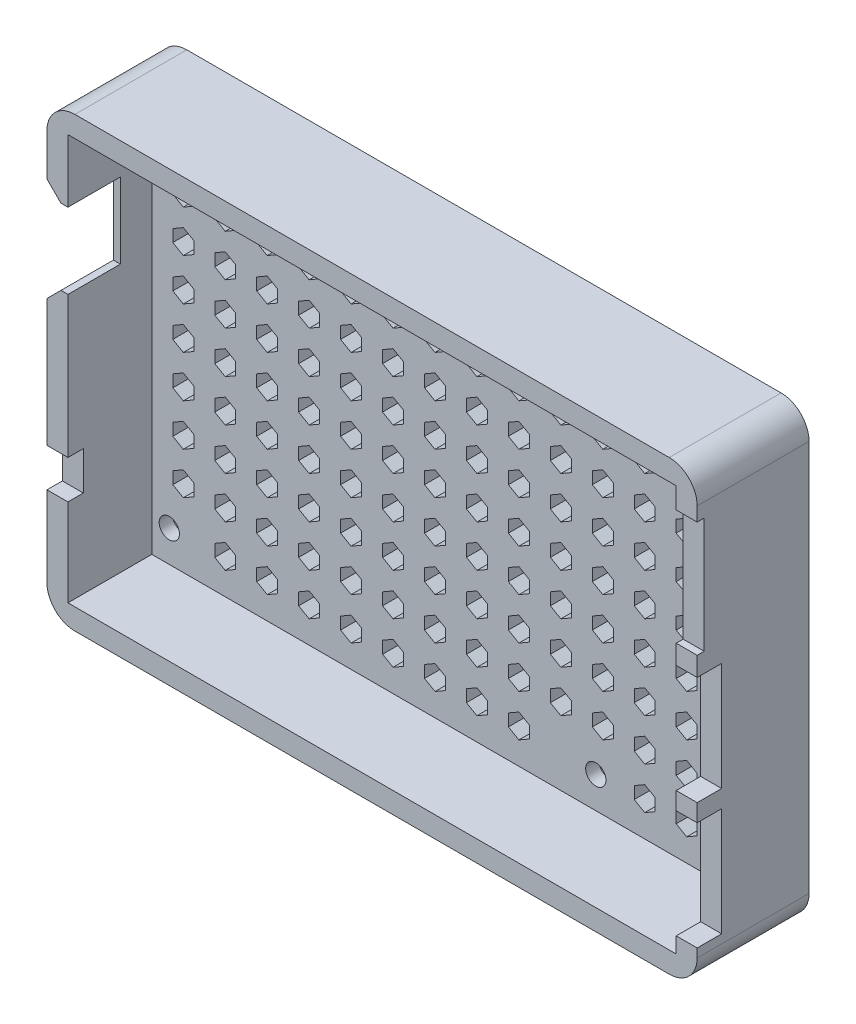
SolidWorks part; units mm, degrees
ref_plane "Přední rovina" through (0, 0, 0) normal (0, 0, 1) x (1, 0, 0)
ref_plane "Horní rovina" through (0, 0, 0) normal (0, 1, 0) x (1, 0, 0)
ref_plane "Pravá rovina" through (0, 0, 0) normal (1, 0, 0) x (0, 0, -1)
sketch "Base sketch" plane through (0, 0, 0) normal (0, 0, 1) x (1, 0, 0)
  line L1 (-46.5, 32) -> (46.5, 32)
  line L2 (-46.5, 32) -> (-46.5, -32)
  line L3 (-46.5, -32) -> (46.5, -32)
  line L4 (46.5, 32) -> (46.5, -32)
  line L5 (-46.5, 32) -> (46.5, -32) construction
  line L6 (-46.5, -32) -> (46.5, 32) construction
  point P0 (0, 0)
  dimension "D1" = 93
  dimension "D2" = 64
extrude "Base" add sketch "Base sketch" along normal blind 16
sketch "Inside cut sketch" plane through (0, 0, 16) normal (0, 0, 1) x (1, 0, 0)
  line L1 (-43.5, 29) -> (43.5, 29)
  line L2 (-43.5, 29) -> (-43.5, -29)
  line L3 (-43.5, -29) -> (43.5, -29)
  line L4 (43.5, 29) -> (43.5, -29)
  line L5 (-43.5, 29) -> (43.5, -29) construction
  line L6 (-43.5, -29) -> (43.5, 29) construction
  point P0 (0, 0)
  dimension "D1" = 58
  dimension "D2" = 87
extrude "Inside cut" cut sketch "Inside cut sketch" against normal blind 12
sketch "Front connectors sketch" plane through (46.5, 0, 0) normal (1, 0, 0) x (0, 0, -1)
  line L0 (-15, -32) -> (-15, 32)
  line L1 (-16, -32) -> (0, -32) construction
  line L2 (-16, 32) -> (0, 32) construction
  line L3 (-12.5, -32) -> (-12.5, 32)
  line L4 (-16, -32) -> (-16, 32) construction
  line L5 (-15, 26) -> (-16, 26)
  line L6 (-15, 26) -> (-15, 9.5)
  line L7 (-15, 9.5) -> (-16, 9.5)
  line L8 (-16, 26) -> (-16, 9.5)
  line L10 (-12.5, 6.75) -> (-16, 6.75)
  line L11 (-12.5, 6.75) -> (-12.5, -8.75)
  line L12 (-12.5, -8.75) -> (-16, -8.75)
  line L13 (-16, 6.75) -> (-16, -8.75)
  line L14 (-12.5, -11.25) -> (-16, -11.25)
  line L15 (-12.5, -11.25) -> (-12.5, -26.75)
  line L16 (-12.5, -26.75) -> (-16, -26.75)
  line L17 (-16, -11.25) -> (-16, -26.75)
  point P23 (-16, 17.75)
  point P25 (-16, -1)
  point P26 (-16, -19)
  dimension "D1" = 1
  dimension "D2" = 3.5
  dimension "D3" = 16.5
  dimension "D4" = 11.25
  dimension "D5" = 30
  dimension "D6" = 15.5
  dimension "D7" = 48
extrude "Front connectors" cut sketch "Front connectors sketch" against normal up to next contours L14 L17 L16 L15 | L12 L13 L10 L11 | L8 L7 L6 L5
sketch "Back connectors sketch" plane through (-46.5, 0, 0) normal (-1, 0, 0) x (0, 0, 1)
  line L0 (16, 32) -> (16, -32) construction
  line L1 (16, 20) -> (8.5, 20)
  line L2 (16, 20) -> (16, 9.2)
  line L3 (16, 9.2) -> (8.5, 9.2)
  line L4 (8.5, 20) -> (8.5, 9.2)
  line L6 (16, -11) -> (13.8, -11)
  line L7 (16, -11) -> (16, -16.5)
  line L8 (16, -16.5) -> (13.8, -16.5)
  line L9 (13.8, -11) -> (13.8, -16.5)
  dimension "D1" = 15.5
  dimension "D2" = 5.5
  dimension "D3" = 2.2
  dimension "D4" = 12
  dimension "D5" = 10.8
  dimension "D6" = 7.5
extrude "Back connectors" cut sketch "Back connectors sketch" against normal up to next
chamfer "Molex angle" distance 2 angle 45 3 edges at (-46.5, 9.2, 12.25) (-46.5, 20, 12.25) (-46.5, 14.6, 8.5)
sketch "Screw holes sketch" plane through (0, 0, 0) normal (0, 0, -1) x (-1, 0, 0)
  line L1 (-20, 24.5) -> (41, 24.5)
  line L2 (-20, 24.5) -> (-20, -24.5)
  line L3 (-20, -24.5) -> (41, -24.5)
  line L4 (41, 24.5) -> (41, -24.5)
  line L5 (-20, 24.5) -> (41, -24.5) construction
  line L6 (-20, -24.5) -> (41, 24.5) construction
  point P0 (10.5, 0)
  dimension "D1" = 5.5
  dimension "D2" = 7.5
  dimension "D3" = 49
  dimension "D4" = 61
hole_wizard "Screw holes" positions "Skica6" profile "Skica7" counterbore size "M2.5" standard "ISO" end condition through all
sketch "Skica6" plane through (0, 0, 0) normal (0, 0, -1) x (-1, 0, 0)
  point P0 (-20, -24.5)
  point P3 (-20, 24.5)
  point P6 (41, 24.5)
  point P9 (41, -24.5)
sketch "Skica7" plane through (20, -24.5, 0) normal (1, 0, 0) x (0, 1, 0)
  line L0 (0, 0) -> (0, 16)
  line L1 (0, 16) -> (1.45, 16)
  line L3 (1.45, 16) -> (1.45, 2.1)
  line L4 (1.45, 2.1) -> (3, 2.1)
  line L5 (3, 2.1) -> (3, 0)
  line L7 (3, 0) -> (0, 0)
  line L11 (0, -6.35) -> (0, 107.95) construction
  dimension "Průměr díry skrz" = 2.9
  dimension "Hloubka díry skrz" = 16
  dimension "Průměr válcového zahloubení" = 6
  dimension "Hloubka válcového zahloubení" = 2.1
fillet "Box rounding" radius 4 4 edges at (-46.5, -32, 8) (-46.5, 32, 8) (46.5, 32, 8) (46.5, -32, 8)
sketch "Ventilation holes sketch" plane through (0, 0, 0) normal (0, 0, -1) x (-1, 0, 0)
  line L0 (-42.5, 32) -> (42.5, 32) construction
  line L1 (-39, 22.2659) -> (-37.5, 23.1319)
  line L2 (-37.5, 23.1319) -> (-37.5, 24.864)
  line L3 (-37.5, 24.864) -> (-39, 25.73)
  line L4 (-39, 25.73) -> (-40.5, 24.864)
  line L5 (-40.5, 24.864) -> (-40.5, 23.1319)
  line L6 (-40.5, 23.1319) -> (-39, 22.2659)
  line L7 (-46.5, -28) -> (-46.5, 28) construction
  line L8 (-33, 22.2659) -> (-31.5, 23.1319)
  line L9 (-31.5, 23.1319) -> (-31.5, 24.864)
  line L10 (-31.5, 24.864) -> (-33, 25.73)
  line L11 (-33, 25.73) -> (-34.5, 24.864)
  line L12 (-34.5, 24.864) -> (-34.5, 23.1319)
  line L13 (-34.5, 23.1319) -> (-33, 22.2659)
  line L14 (-27, 22.2659) -> (-25.5, 23.1319)
  line L15 (-25.5, 23.1319) -> (-25.5, 24.864)
  line L16 (-25.5, 24.864) -> (-27, 25.73)
  line L17 (-27, 25.73) -> (-28.5, 24.864)
  line L18 (-28.5, 24.864) -> (-28.5, 23.1319)
  line L19 (-28.5, 23.1319) -> (-27, 22.2659)
  line L20 (-21, 22.2659) -> (-19.5, 23.1319)
  line L21 (-19.5, 23.1319) -> (-19.5, 24.864)
  line L22 (-19.5, 24.864) -> (-21, 25.73)
  line L23 (-21, 25.73) -> (-22.5, 24.864)
  line L24 (-22.5, 24.864) -> (-22.5, 23.1319)
  line L25 (-22.5, 23.1319) -> (-21, 22.2659)
  line L26 (-15, 22.2659) -> (-13.5, 23.1319)
  line L27 (-13.5, 23.1319) -> (-13.5, 24.864)
  line L28 (-13.5, 24.864) -> (-15, 25.73)
  line L29 (-15, 25.73) -> (-16.5, 24.864)
  line L30 (-16.5, 24.864) -> (-16.5, 23.1319)
  line L31 (-16.5, 23.1319) -> (-15, 22.2659)
  line L32 (-9, 22.2659) -> (-7.5, 23.1319)
  line L33 (-7.5, 23.1319) -> (-7.5, 24.864)
  line L34 (-7.5, 24.864) -> (-9, 25.73)
  line L35 (-9, 25.73) -> (-10.5, 24.864)
  line L36 (-10.5, 24.864) -> (-10.5, 23.1319)
  line L37 (-10.5, 23.1319) -> (-9, 22.2659)
  line L38 (-3, 22.2659) -> (-1.5, 23.1319)
  line L39 (-1.5, 23.1319) -> (-1.5, 24.864)
  line L40 (-1.5, 24.864) -> (-3, 25.73)
  line L41 (-3, 25.73) -> (-4.5, 24.864)
  line L42 (-4.5, 24.864) -> (-4.5, 23.1319)
  line L43 (-4.5, 23.1319) -> (-3, 22.2659)
  line L44 (3, 22.2659) -> (4.5, 23.1319)
  line L45 (4.5, 23.1319) -> (4.5, 24.864)
  line L46 (4.5, 24.864) -> (3, 25.73)
  line L47 (3, 25.73) -> (1.5, 24.864)
  line L48 (1.5, 24.864) -> (1.5, 23.1319)
  line L49 (1.5, 23.1319) -> (3, 22.2659)
  line L50 (9, 22.2659) -> (10.5, 23.1319)
  line L51 (10.5, 23.1319) -> (10.5, 24.864)
  line L52 (10.5, 24.864) -> (9, 25.73)
  line L53 (9, 25.73) -> (7.5, 24.864)
  line L54 (7.5, 24.864) -> (7.5, 23.1319)
  line L55 (7.5, 23.1319) -> (9, 22.2659)
  line L56 (15, 22.2659) -> (16.5, 23.1319)
  line L57 (16.5, 23.1319) -> (16.5, 24.864)
  line L58 (16.5, 24.864) -> (15, 25.73)
  line L59 (15, 25.73) -> (13.5, 24.864)
  line L60 (13.5, 24.864) -> (13.5, 23.1319)
  line L61 (13.5, 23.1319) -> (15, 22.2659)
  line L62 (21, 22.2659) -> (22.5, 23.1319)
  line L63 (22.5, 23.1319) -> (22.5, 24.864)
  line L64 (22.5, 24.864) -> (21, 25.73)
  line L65 (21, 25.73) -> (19.5, 24.864)
  line L66 (19.5, 24.864) -> (19.5, 23.1319)
  line L67 (19.5, 23.1319) -> (21, 22.2659)
  line L68 (27, 22.2659) -> (28.5, 23.1319)
  line L69 (28.5, 23.1319) -> (28.5, 24.864)
  line L70 (28.5, 24.864) -> (27, 25.73)
  line L71 (27, 25.73) -> (25.5, 24.864)
  line L72 (25.5, 24.864) -> (25.5, 23.1319)
  line L73 (25.5, 23.1319) -> (27, 22.2659)
  line L74 (33, 22.2659) -> (34.5, 23.1319)
  line L75 (34.5, 23.1319) -> (34.5, 24.864)
  line L76 (34.5, 24.864) -> (33, 25.73)
  line L77 (33, 25.73) -> (31.5, 24.864)
  line L78 (31.5, 24.864) -> (31.5, 23.1319)
  line L79 (31.5, 23.1319) -> (33, 22.2659)
  line L80 (39, 22.2659) -> (40.5, 23.1319)
  line L81 (40.5, 23.1319) -> (40.5, 24.864)
  line L82 (40.5, 24.864) -> (39, 25.73)
  line L83 (39, 25.73) -> (37.5, 24.864)
  line L84 (37.5, 24.864) -> (37.5, 23.1319)
  line L85 (37.5, 23.1319) -> (39, 22.2659)
  line L86 (-33, 16.2659) -> (-31.5, 17.1319)
  line L87 (-31.5, 17.1319) -> (-31.5, 18.864)
  line L88 (-31.5, 18.864) -> (-33, 19.73)
  line L89 (-33, 19.73) -> (-34.5, 18.864)
  line L90 (-34.5, 18.864) -> (-34.5, 17.1319)
  line L91 (-34.5, 17.1319) -> (-33, 16.2659)
  line L92 (-27, 16.2659) -> (-25.5, 17.1319)
  line L93 (-25.5, 17.1319) -> (-25.5, 18.864)
  line L94 (-25.5, 18.864) -> (-27, 19.73)
  line L95 (-27, 19.73) -> (-28.5, 18.864)
  line L96 (-28.5, 18.864) -> (-28.5, 17.1319)
  line L97 (-28.5, 17.1319) -> (-27, 16.2659)
  line L98 (-21, 16.2659) -> (-19.5, 17.1319)
  line L99 (-19.5, 17.1319) -> (-19.5, 18.864)
  line L100 (-19.5, 18.864) -> (-21, 19.73)
  line L101 (-21, 19.73) -> (-22.5, 18.864)
  line L102 (-22.5, 18.864) -> (-22.5, 17.1319)
  line L103 (-22.5, 17.1319) -> (-21, 16.2659)
  line L104 (-15, 16.2659) -> (-13.5, 17.1319)
  line L105 (-13.5, 17.1319) -> (-13.5, 18.864)
  line L106 (-13.5, 18.864) -> (-15, 19.73)
  line L107 (-15, 19.73) -> (-16.5, 18.864)
  line L108 (-16.5, 18.864) -> (-16.5, 17.1319)
  line L109 (-16.5, 17.1319) -> (-15, 16.2659)
  line L110 (-9, 16.2659) -> (-7.5, 17.1319)
  line L111 (-7.5, 17.1319) -> (-7.5, 18.864)
  line L112 (-7.5, 18.864) -> (-9, 19.73)
  line L113 (-9, 19.73) -> (-10.5, 18.864)
  line L114 (-10.5, 18.864) -> (-10.5, 17.1319)
  line L115 (-10.5, 17.1319) -> (-9, 16.2659)
  line L116 (-3, 16.2659) -> (-1.5, 17.1319)
  line L117 (-1.5, 17.1319) -> (-1.5, 18.864)
  line L118 (-1.5, 18.864) -> (-3, 19.73)
  line L119 (-3, 19.73) -> (-4.5, 18.864)
  line L120 (-4.5, 18.864) -> (-4.5, 17.1319)
  line L121 (-4.5, 17.1319) -> (-3, 16.2659)
  line L122 (3, 16.2659) -> (4.5, 17.1319)
  line L123 (4.5, 17.1319) -> (4.5, 18.864)
  line L124 (4.5, 18.864) -> (3, 19.73)
  line L125 (3, 19.73) -> (1.5, 18.864)
  line L126 (1.5, 18.864) -> (1.5, 17.1319)
  line L127 (1.5, 17.1319) -> (3, 16.2659)
  line L128 (9, 16.2659) -> (10.5, 17.1319)
  line L129 (10.5, 17.1319) -> (10.5, 18.864)
  line L130 (10.5, 18.864) -> (9, 19.73)
  line L131 (9, 19.73) -> (7.5, 18.864)
  line L132 (7.5, 18.864) -> (7.5, 17.1319)
  line L133 (7.5, 17.1319) -> (9, 16.2659)
  line L134 (15, 16.2659) -> (16.5, 17.1319)
  line L135 (16.5, 17.1319) -> (16.5, 18.864)
  line L136 (16.5, 18.864) -> (15, 19.73)
  line L137 (15, 19.73) -> (13.5, 18.864)
  line L138 (13.5, 18.864) -> (13.5, 17.1319)
  line L139 (13.5, 17.1319) -> (15, 16.2659)
  line L140 (21, 16.2659) -> (22.5, 17.1319)
  line L141 (22.5, 17.1319) -> (22.5, 18.864)
  line L142 (22.5, 18.864) -> (21, 19.73)
  line L143 (21, 19.73) -> (19.5, 18.864)
  line L144 (19.5, 18.864) -> (19.5, 17.1319)
  line L145 (19.5, 17.1319) -> (21, 16.2659)
  line L146 (27, 16.2659) -> (28.5, 17.1319)
  line L147 (28.5, 17.1319) -> (28.5, 18.864)
  line L148 (28.5, 18.864) -> (27, 19.73)
  line L149 (27, 19.73) -> (25.5, 18.864)
  line L150 (25.5, 18.864) -> (25.5, 17.1319)
  line L151 (25.5, 17.1319) -> (27, 16.2659)
  line L152 (33, 16.2659) -> (34.5, 17.1319)
  line L153 (34.5, 17.1319) -> (34.5, 18.864)
  line L154 (34.5, 18.864) -> (33, 19.73)
  line L155 (33, 19.73) -> (31.5, 18.864)
  line L156 (31.5, 18.864) -> (31.5, 17.1319)
  line L157 (31.5, 17.1319) -> (33, 16.2659)
  line L158 (39, 16.2659) -> (40.5, 17.1319)
  line L159 (40.5, 17.1319) -> (40.5, 18.864)
  line L160 (40.5, 18.864) -> (39, 19.73)
  line L161 (39, 19.73) -> (37.5, 18.864)
  line L162 (37.5, 18.864) -> (37.5, 17.1319)
  line L163 (37.5, 17.1319) -> (39, 16.2659)
  line L164 (-33, 10.2659) -> (-31.5, 11.1319)
  line L165 (-31.5, 11.1319) -> (-31.5, 12.864)
  line L166 (-31.5, 12.864) -> (-33, 13.73)
  line L167 (-33, 13.73) -> (-34.5, 12.864)
  line L168 (-34.5, 12.864) -> (-34.5, 11.1319)
  line L169 (-34.5, 11.1319) -> (-33, 10.2659)
  line L170 (-27, 10.2659) -> (-25.5, 11.1319)
  line L171 (-25.5, 11.1319) -> (-25.5, 12.864)
  line L172 (-25.5, 12.864) -> (-27, 13.73)
  line L173 (-27, 13.73) -> (-28.5, 12.864)
  line L174 (-28.5, 12.864) -> (-28.5, 11.1319)
  line L175 (-28.5, 11.1319) -> (-27, 10.2659)
  line L176 (-21, 10.2659) -> (-19.5, 11.1319)
  line L177 (-19.5, 11.1319) -> (-19.5, 12.864)
  line L178 (-19.5, 12.864) -> (-21, 13.73)
  line L179 (-21, 13.73) -> (-22.5, 12.864)
  line L180 (-22.5, 12.864) -> (-22.5, 11.1319)
  line L181 (-22.5, 11.1319) -> (-21, 10.2659)
  line L182 (-15, 10.2659) -> (-13.5, 11.1319)
  line L183 (-13.5, 11.1319) -> (-13.5, 12.864)
  line L184 (-13.5, 12.864) -> (-15, 13.73)
  line L185 (-15, 13.73) -> (-16.5, 12.864)
  line L186 (-16.5, 12.864) -> (-16.5, 11.1319)
  line L187 (-16.5, 11.1319) -> (-15, 10.2659)
  line L188 (-9, 10.2659) -> (-7.5, 11.1319)
  line L189 (-7.5, 11.1319) -> (-7.5, 12.864)
  line L190 (-7.5, 12.864) -> (-9, 13.73)
  line L191 (-9, 13.73) -> (-10.5, 12.864)
  line L192 (-10.5, 12.864) -> (-10.5, 11.1319)
  line L193 (-10.5, 11.1319) -> (-9, 10.2659)
  line L194 (-3, 10.2659) -> (-1.5, 11.1319)
  line L195 (-1.5, 11.1319) -> (-1.5, 12.864)
  line L196 (-1.5, 12.864) -> (-3, 13.73)
  line L197 (-3, 13.73) -> (-4.5, 12.864)
  line L198 (-4.5, 12.864) -> (-4.5, 11.1319)
  line L199 (-4.5, 11.1319) -> (-3, 10.2659)
  line L200 (3, 10.2659) -> (4.5, 11.1319)
  line L201 (4.5, 11.1319) -> (4.5, 12.864)
  line L202 (4.5, 12.864) -> (3, 13.73)
  line L203 (3, 13.73) -> (1.5, 12.864)
  line L204 (1.5, 12.864) -> (1.5, 11.1319)
  line L205 (1.5, 11.1319) -> (3, 10.2659)
  line L206 (9, 10.2659) -> (10.5, 11.1319)
  line L207 (10.5, 11.1319) -> (10.5, 12.864)
  line L208 (10.5, 12.864) -> (9, 13.73)
  line L209 (9, 13.73) -> (7.5, 12.864)
  line L210 (7.5, 12.864) -> (7.5, 11.1319)
  line L211 (7.5, 11.1319) -> (9, 10.2659)
  line L212 (15, 10.2659) -> (16.5, 11.1319)
  line L213 (16.5, 11.1319) -> (16.5, 12.864)
  line L214 (16.5, 12.864) -> (15, 13.73)
  line L215 (15, 13.73) -> (13.5, 12.864)
  line L216 (13.5, 12.864) -> (13.5, 11.1319)
  line L217 (13.5, 11.1319) -> (15, 10.2659)
  line L218 (21, 10.2659) -> (22.5, 11.1319)
  line L219 (22.5, 11.1319) -> (22.5, 12.864)
  line L220 (22.5, 12.864) -> (21, 13.73)
  line L221 (21, 13.73) -> (19.5, 12.864)
  line L222 (19.5, 12.864) -> (19.5, 11.1319)
  line L223 (19.5, 11.1319) -> (21, 10.2659)
  line L224 (27, 10.2659) -> (28.5, 11.1319)
  line L225 (28.5, 11.1319) -> (28.5, 12.864)
  line L226 (28.5, 12.864) -> (27, 13.73)
  line L227 (27, 13.73) -> (25.5, 12.864)
  line L228 (25.5, 12.864) -> (25.5, 11.1319)
  line L229 (25.5, 11.1319) -> (27, 10.2659)
  line L230 (33, 10.2659) -> (34.5, 11.1319)
  line L231 (34.5, 11.1319) -> (34.5, 12.864)
  line L232 (34.5, 12.864) -> (33, 13.73)
  line L233 (33, 13.73) -> (31.5, 12.864)
  line L234 (31.5, 12.864) -> (31.5, 11.1319)
  line L235 (31.5, 11.1319) -> (33, 10.2659)
  line L236 (39, 10.2659) -> (40.5, 11.1319)
  line L237 (40.5, 11.1319) -> (40.5, 12.864)
  line L238 (40.5, 12.864) -> (39, 13.73)
  line L239 (39, 13.73) -> (37.5, 12.864)
  line L240 (37.5, 12.864) -> (37.5, 11.1319)
  line L241 (37.5, 11.1319) -> (39, 10.2659)
  line L242 (-33, 4.2659) -> (-31.5, 5.1319)
  line L243 (-31.5, 5.1319) -> (-31.5, 6.864)
  line L244 (-31.5, 6.864) -> (-33, 7.73)
  line L245 (-33, 7.73) -> (-34.5, 6.864)
  line L246 (-34.5, 6.864) -> (-34.5, 5.1319)
  line L247 (-34.5, 5.1319) -> (-33, 4.2659)
  line L248 (-27, 4.2659) -> (-25.5, 5.1319)
  line L249 (-25.5, 5.1319) -> (-25.5, 6.864)
  line L250 (-25.5, 6.864) -> (-27, 7.73)
  line L251 (-27, 7.73) -> (-28.5, 6.864)
  line L252 (-28.5, 6.864) -> (-28.5, 5.1319)
  line L253 (-28.5, 5.1319) -> (-27, 4.2659)
  line L254 (-21, 4.2659) -> (-19.5, 5.1319)
  line L255 (-19.5, 5.1319) -> (-19.5, 6.864)
  line L256 (-19.5, 6.864) -> (-21, 7.73)
  line L257 (-21, 7.73) -> (-22.5, 6.864)
  line L258 (-22.5, 6.864) -> (-22.5, 5.1319)
  line L259 (-22.5, 5.1319) -> (-21, 4.2659)
  line L260 (-15, 4.2659) -> (-13.5, 5.1319)
  line L261 (-13.5, 5.1319) -> (-13.5, 6.864)
  line L262 (-13.5, 6.864) -> (-15, 7.73)
  line L263 (-15, 7.73) -> (-16.5, 6.864)
  line L264 (-16.5, 6.864) -> (-16.5, 5.1319)
  line L265 (-16.5, 5.1319) -> (-15, 4.2659)
  line L266 (-9, 4.2659) -> (-7.5, 5.1319)
  line L267 (-7.5, 5.1319) -> (-7.5, 6.864)
  line L268 (-7.5, 6.864) -> (-9, 7.73)
  line L269 (-9, 7.73) -> (-10.5, 6.864)
  line L270 (-10.5, 6.864) -> (-10.5, 5.1319)
  line L271 (-10.5, 5.1319) -> (-9, 4.2659)
  line L272 (-3, 4.2659) -> (-1.5, 5.1319)
  line L273 (-1.5, 5.1319) -> (-1.5, 6.864)
  line L274 (-1.5, 6.864) -> (-3, 7.73)
  line L275 (-3, 7.73) -> (-4.5, 6.864)
  line L276 (-4.5, 6.864) -> (-4.5, 5.1319)
  line L277 (-4.5, 5.1319) -> (-3, 4.2659)
  line L278 (3, 4.2659) -> (4.5, 5.1319)
  line L279 (4.5, 5.1319) -> (4.5, 6.864)
  line L280 (4.5, 6.864) -> (3, 7.73)
  line L281 (3, 7.73) -> (1.5, 6.864)
  line L282 (1.5, 6.864) -> (1.5, 5.1319)
  line L283 (1.5, 5.1319) -> (3, 4.2659)
  line L284 (9, 4.2659) -> (10.5, 5.1319)
  line L285 (10.5, 5.1319) -> (10.5, 6.864)
  line L286 (10.5, 6.864) -> (9, 7.73)
  line L287 (9, 7.73) -> (7.5, 6.864)
  line L288 (7.5, 6.864) -> (7.5, 5.1319)
  line L289 (7.5, 5.1319) -> (9, 4.2659)
  line L290 (15, 4.2659) -> (16.5, 5.1319)
  line L291 (16.5, 5.1319) -> (16.5, 6.864)
  line L292 (16.5, 6.864) -> (15, 7.73)
  line L293 (15, 7.73) -> (13.5, 6.864)
  line L294 (13.5, 6.864) -> (13.5, 5.1319)
  line L295 (13.5, 5.1319) -> (15, 4.2659)
  line L296 (21, 4.2659) -> (22.5, 5.1319)
  line L297 (22.5, 5.1319) -> (22.5, 6.864)
  line L298 (22.5, 6.864) -> (21, 7.73)
  line L299 (21, 7.73) -> (19.5, 6.864)
  line L300 (19.5, 6.864) -> (19.5, 5.1319)
  line L301 (19.5, 5.1319) -> (21, 4.2659)
  line L302 (27, 4.2659) -> (28.5, 5.1319)
  line L303 (28.5, 5.1319) -> (28.5, 6.864)
  line L304 (28.5, 6.864) -> (27, 7.73)
  line L305 (27, 7.73) -> (25.5, 6.864)
  line L306 (25.5, 6.864) -> (25.5, 5.1319)
  line L307 (25.5, 5.1319) -> (27, 4.2659)
  line L308 (33, 4.2659) -> (34.5, 5.1319)
  line L309 (34.5, 5.1319) -> (34.5, 6.864)
  line L310 (34.5, 6.864) -> (33, 7.73)
  line L311 (33, 7.73) -> (31.5, 6.864)
  line L312 (31.5, 6.864) -> (31.5, 5.1319)
  line L313 (31.5, 5.1319) -> (33, 4.2659)
  line L314 (39, 4.2659) -> (40.5, 5.1319)
  line L315 (40.5, 5.1319) -> (40.5, 6.864)
  line L316 (40.5, 6.864) -> (39, 7.73)
  line L317 (39, 7.73) -> (37.5, 6.864)
  line L318 (37.5, 6.864) -> (37.5, 5.1319)
  line L319 (37.5, 5.1319) -> (39, 4.2659)
  line L320 (-33, -1.7341) -> (-31.5, -0.8681)
  line L321 (-31.5, -0.8681) -> (-31.5, 0.864)
  line L322 (-31.5, 0.864) -> (-33, 1.73)
  line L323 (-33, 1.73) -> (-34.5, 0.864)
  line L324 (-34.5, 0.864) -> (-34.5, -0.8681)
  line L325 (-34.5, -0.8681) -> (-33, -1.7341)
  line L326 (-27, -1.7341) -> (-25.5, -0.8681)
  line L327 (-25.5, -0.8681) -> (-25.5, 0.864)
  line L328 (-25.5, 0.864) -> (-27, 1.73)
  line L329 (-27, 1.73) -> (-28.5, 0.864)
  line L330 (-28.5, 0.864) -> (-28.5, -0.8681)
  line L331 (-28.5, -0.8681) -> (-27, -1.7341)
  line L332 (-21, -1.7341) -> (-19.5, -0.8681)
  line L333 (-19.5, -0.8681) -> (-19.5, 0.864)
  line L334 (-19.5, 0.864) -> (-21, 1.73)
  line L335 (-21, 1.73) -> (-22.5, 0.864)
  line L336 (-22.5, 0.864) -> (-22.5, -0.8681)
  line L337 (-22.5, -0.8681) -> (-21, -1.7341)
  line L338 (-15, -1.7341) -> (-13.5, -0.8681)
  line L339 (-13.5, -0.8681) -> (-13.5, 0.864)
  line L340 (-13.5, 0.864) -> (-15, 1.73)
  line L341 (-15, 1.73) -> (-16.5, 0.864)
  line L342 (-16.5, 0.864) -> (-16.5, -0.8681)
  line L343 (-16.5, -0.8681) -> (-15, -1.7341)
  line L344 (-9, -1.7341) -> (-7.5, -0.8681)
  line L345 (-7.5, -0.8681) -> (-7.5, 0.864)
  line L346 (-7.5, 0.864) -> (-9, 1.73)
  line L347 (-9, 1.73) -> (-10.5, 0.864)
  line L348 (-10.5, 0.864) -> (-10.5, -0.8681)
  line L349 (-10.5, -0.8681) -> (-9, -1.7341)
  line L350 (-3, -1.7341) -> (-1.5, -0.8681)
  line L351 (-1.5, -0.8681) -> (-1.5, 0.864)
  line L352 (-1.5, 0.864) -> (-3, 1.73)
  line L353 (-3, 1.73) -> (-4.5, 0.864)
  line L354 (-4.5, 0.864) -> (-4.5, -0.8681)
  line L355 (-4.5, -0.8681) -> (-3, -1.7341)
  line L356 (3, -1.7341) -> (4.5, -0.8681)
  line L357 (4.5, -0.8681) -> (4.5, 0.864)
  line L358 (4.5, 0.864) -> (3, 1.73)
  line L359 (3, 1.73) -> (1.5, 0.864)
  line L360 (1.5, 0.864) -> (1.5, -0.8681)
  line L361 (1.5, -0.8681) -> (3, -1.7341)
  line L362 (9, -1.7341) -> (10.5, -0.8681)
  line L363 (10.5, -0.8681) -> (10.5, 0.864)
  line L364 (10.5, 0.864) -> (9, 1.73)
  line L365 (9, 1.73) -> (7.5, 0.864)
  line L366 (7.5, 0.864) -> (7.5, -0.8681)
  line L367 (7.5, -0.8681) -> (9, -1.7341)
  line L368 (15, -1.7341) -> (16.5, -0.8681)
  line L369 (16.5, -0.8681) -> (16.5, 0.864)
  line L370 (16.5, 0.864) -> (15, 1.73)
  line L371 (15, 1.73) -> (13.5, 0.864)
  line L372 (13.5, 0.864) -> (13.5, -0.8681)
  line L373 (13.5, -0.8681) -> (15, -1.7341)
  line L374 (21, -1.7341) -> (22.5, -0.8681)
  line L375 (22.5, -0.8681) -> (22.5, 0.864)
  line L376 (22.5, 0.864) -> (21, 1.73)
  line L377 (21, 1.73) -> (19.5, 0.864)
  line L378 (19.5, 0.864) -> (19.5, -0.8681)
  line L379 (19.5, -0.8681) -> (21, -1.7341)
  line L380 (27, -1.7341) -> (28.5, -0.8681)
  line L381 (28.5, -0.8681) -> (28.5, 0.864)
  line L382 (28.5, 0.864) -> (27, 1.73)
  line L383 (27, 1.73) -> (25.5, 0.864)
  line L384 (25.5, 0.864) -> (25.5, -0.8681)
  line L385 (25.5, -0.8681) -> (27, -1.7341)
  line L386 (33, -1.7341) -> (34.5, -0.8681)
  line L387 (34.5, -0.8681) -> (34.5, 0.864)
  line L388 (34.5, 0.864) -> (33, 1.73)
  line L389 (33, 1.73) -> (31.5, 0.864)
  line L390 (31.5, 0.864) -> (31.5, -0.8681)
  line L391 (31.5, -0.8681) -> (33, -1.7341)
  line L392 (39, -1.7341) -> (40.5, -0.8681)
  line L393 (40.5, -0.8681) -> (40.5, 0.864)
  line L394 (40.5, 0.864) -> (39, 1.73)
  line L395 (39, 1.73) -> (37.5, 0.864)
  line L396 (37.5, 0.864) -> (37.5, -0.8681)
  line L397 (37.5, -0.8681) -> (39, -1.7341)
  line L398 (-33, -7.7341) -> (-31.5, -6.8681)
  line L399 (-31.5, -6.8681) -> (-31.5, -5.136)
  line L400 (-31.5, -5.136) -> (-33, -4.27)
  line L401 (-33, -4.27) -> (-34.5, -5.136)
  line L402 (-34.5, -5.136) -> (-34.5, -6.8681)
  line L403 (-34.5, -6.8681) -> (-33, -7.7341)
  line L404 (-27, -7.7341) -> (-25.5, -6.8681)
  line L405 (-25.5, -6.8681) -> (-25.5, -5.136)
  line L406 (-25.5, -5.136) -> (-27, -4.27)
  line L407 (-27, -4.27) -> (-28.5, -5.136)
  line L408 (-28.5, -5.136) -> (-28.5, -6.8681)
  line L409 (-28.5, -6.8681) -> (-27, -7.7341)
  line L410 (-21, -7.7341) -> (-19.5, -6.8681)
  line L411 (-19.5, -6.8681) -> (-19.5, -5.136)
  line L412 (-19.5, -5.136) -> (-21, -4.27)
  line L413 (-21, -4.27) -> (-22.5, -5.136)
  line L414 (-22.5, -5.136) -> (-22.5, -6.8681)
  line L415 (-22.5, -6.8681) -> (-21, -7.7341)
  line L416 (-15, -7.7341) -> (-13.5, -6.8681)
  line L417 (-13.5, -6.8681) -> (-13.5, -5.136)
  line L418 (-13.5, -5.136) -> (-15, -4.27)
  line L419 (-15, -4.27) -> (-16.5, -5.136)
  line L420 (-16.5, -5.136) -> (-16.5, -6.8681)
  line L421 (-16.5, -6.8681) -> (-15, -7.7341)
  line L422 (-9, -7.7341) -> (-7.5, -6.8681)
  line L423 (-7.5, -6.8681) -> (-7.5, -5.136)
  line L424 (-7.5, -5.136) -> (-9, -4.27)
  line L425 (-9, -4.27) -> (-10.5, -5.136)
  line L426 (-10.5, -5.136) -> (-10.5, -6.8681)
  line L427 (-10.5, -6.8681) -> (-9, -7.7341)
  line L428 (-3, -7.7341) -> (-1.5, -6.8681)
  line L429 (-1.5, -6.8681) -> (-1.5, -5.136)
  line L430 (-1.5, -5.136) -> (-3, -4.27)
  line L431 (-3, -4.27) -> (-4.5, -5.136)
  line L432 (-4.5, -5.136) -> (-4.5, -6.8681)
  line L433 (-4.5, -6.8681) -> (-3, -7.7341)
  line L434 (3, -7.7341) -> (4.5, -6.8681)
  line L435 (4.5, -6.8681) -> (4.5, -5.136)
  line L436 (4.5, -5.136) -> (3, -4.27)
  line L437 (3, -4.27) -> (1.5, -5.136)
  line L438 (1.5, -5.136) -> (1.5, -6.8681)
  line L439 (1.5, -6.8681) -> (3, -7.7341)
  line L440 (9, -7.7341) -> (10.5, -6.8681)
  line L441 (10.5, -6.8681) -> (10.5, -5.136)
  line L442 (10.5, -5.136) -> (9, -4.27)
  line L443 (9, -4.27) -> (7.5, -5.136)
  line L444 (7.5, -5.136) -> (7.5, -6.8681)
  line L445 (7.5, -6.8681) -> (9, -7.7341)
  line L446 (15, -7.7341) -> (16.5, -6.8681)
  line L447 (16.5, -6.8681) -> (16.5, -5.136)
  line L448 (16.5, -5.136) -> (15, -4.27)
  line L449 (15, -4.27) -> (13.5, -5.136)
  line L450 (13.5, -5.136) -> (13.5, -6.8681)
  line L451 (13.5, -6.8681) -> (15, -7.7341)
  line L452 (21, -7.7341) -> (22.5, -6.8681)
  line L453 (22.5, -6.8681) -> (22.5, -5.136)
  line L454 (22.5, -5.136) -> (21, -4.27)
  line L455 (21, -4.27) -> (19.5, -5.136)
  line L456 (19.5, -5.136) -> (19.5, -6.8681)
  line L457 (19.5, -6.8681) -> (21, -7.7341)
  line L458 (27, -7.7341) -> (28.5, -6.8681)
  line L459 (28.5, -6.8681) -> (28.5, -5.136)
  line L460 (28.5, -5.136) -> (27, -4.27)
  line L461 (27, -4.27) -> (25.5, -5.136)
  line L462 (25.5, -5.136) -> (25.5, -6.8681)
  line L463 (25.5, -6.8681) -> (27, -7.7341)
  line L464 (33, -7.7341) -> (34.5, -6.8681)
  line L465 (34.5, -6.8681) -> (34.5, -5.136)
  line L466 (34.5, -5.136) -> (33, -4.27)
  line L467 (33, -4.27) -> (31.5, -5.136)
  line L468 (31.5, -5.136) -> (31.5, -6.8681)
  line L469 (31.5, -6.8681) -> (33, -7.7341)
  line L470 (39, -7.7341) -> (40.5, -6.8681)
  line L471 (40.5, -6.8681) -> (40.5, -5.136)
  line L472 (40.5, -5.136) -> (39, -4.27)
  line L473 (39, -4.27) -> (37.5, -5.136)
  line L474 (37.5, -5.136) -> (37.5, -6.8681)
  line L475 (37.5, -6.8681) -> (39, -7.7341)
  line L476 (-33, -13.7341) -> (-31.5, -12.8681)
  line L477 (-31.5, -12.8681) -> (-31.5, -11.136)
  line L478 (-31.5, -11.136) -> (-33, -10.27)
  line L479 (-33, -10.27) -> (-34.5, -11.136)
  line L480 (-34.5, -11.136) -> (-34.5, -12.8681)
  line L481 (-34.5, -12.8681) -> (-33, -13.7341)
  line L482 (-27, -13.7341) -> (-25.5, -12.8681)
  line L483 (-25.5, -12.8681) -> (-25.5, -11.136)
  line L484 (-25.5, -11.136) -> (-27, -10.27)
  line L485 (-27, -10.27) -> (-28.5, -11.136)
  line L486 (-28.5, -11.136) -> (-28.5, -12.8681)
  line L487 (-28.5, -12.8681) -> (-27, -13.7341)
  line L488 (-21, -13.7341) -> (-19.5, -12.8681)
  line L489 (-19.5, -12.8681) -> (-19.5, -11.136)
  line L490 (-19.5, -11.136) -> (-21, -10.27)
  line L491 (-21, -10.27) -> (-22.5, -11.136)
  line L492 (-22.5, -11.136) -> (-22.5, -12.8681)
  line L493 (-22.5, -12.8681) -> (-21, -13.7341)
  line L494 (-15, -13.7341) -> (-13.5, -12.8681)
  line L495 (-13.5, -12.8681) -> (-13.5, -11.136)
  line L496 (-13.5, -11.136) -> (-15, -10.27)
  line L497 (-15, -10.27) -> (-16.5, -11.136)
  line L498 (-16.5, -11.136) -> (-16.5, -12.8681)
  line L499 (-16.5, -12.8681) -> (-15, -13.7341)
  line L500 (-9, -13.7341) -> (-7.5, -12.8681)
  line L501 (-7.5, -12.8681) -> (-7.5, -11.136)
  line L502 (-7.5, -11.136) -> (-9, -10.27)
  line L503 (-9, -10.27) -> (-10.5, -11.136)
  line L504 (-10.5, -11.136) -> (-10.5, -12.8681)
  line L505 (-10.5, -12.8681) -> (-9, -13.7341)
  line L506 (-3, -13.7341) -> (-1.5, -12.8681)
  line L507 (-1.5, -12.8681) -> (-1.5, -11.136)
  line L508 (-1.5, -11.136) -> (-3, -10.27)
  line L509 (-3, -10.27) -> (-4.5, -11.136)
  line L510 (-4.5, -11.136) -> (-4.5, -12.8681)
  line L511 (-4.5, -12.8681) -> (-3, -13.7341)
  line L512 (3, -13.7341) -> (4.5, -12.8681)
  line L513 (4.5, -12.8681) -> (4.5, -11.136)
  line L514 (4.5, -11.136) -> (3, -10.27)
  line L515 (3, -10.27) -> (1.5, -11.136)
  line L516 (1.5, -11.136) -> (1.5, -12.8681)
  line L517 (1.5, -12.8681) -> (3, -13.7341)
  line L518 (9, -13.7341) -> (10.5, -12.8681)
  line L519 (10.5, -12.8681) -> (10.5, -11.136)
  line L520 (10.5, -11.136) -> (9, -10.27)
  line L521 (9, -10.27) -> (7.5, -11.136)
  line L522 (7.5, -11.136) -> (7.5, -12.8681)
  line L523 (7.5, -12.8681) -> (9, -13.7341)
  line L524 (15, -13.7341) -> (16.5, -12.8681)
  line L525 (16.5, -12.8681) -> (16.5, -11.136)
  line L526 (16.5, -11.136) -> (15, -10.27)
  line L527 (15, -10.27) -> (13.5, -11.136)
  line L528 (13.5, -11.136) -> (13.5, -12.8681)
  line L529 (13.5, -12.8681) -> (15, -13.7341)
  line L530 (21, -13.7341) -> (22.5, -12.8681)
  line L531 (22.5, -12.8681) -> (22.5, -11.136)
  line L532 (22.5, -11.136) -> (21, -10.27)
  line L533 (21, -10.27) -> (19.5, -11.136)
  line L534 (19.5, -11.136) -> (19.5, -12.8681)
  line L535 (19.5, -12.8681) -> (21, -13.7341)
  line L536 (27, -13.7341) -> (28.5, -12.8681)
  line L537 (28.5, -12.8681) -> (28.5, -11.136)
  line L538 (28.5, -11.136) -> (27, -10.27)
  line L539 (27, -10.27) -> (25.5, -11.136)
  line L540 (25.5, -11.136) -> (25.5, -12.8681)
  line L541 (25.5, -12.8681) -> (27, -13.7341)
  line L542 (33, -13.7341) -> (34.5, -12.8681)
  line L543 (34.5, -12.8681) -> (34.5, -11.136)
  line L544 (34.5, -11.136) -> (33, -10.27)
  line L545 (33, -10.27) -> (31.5, -11.136)
  line L546 (31.5, -11.136) -> (31.5, -12.8681)
  line L547 (31.5, -12.8681) -> (33, -13.7341)
  line L548 (39, -13.7341) -> (40.5, -12.8681)
  line L549 (40.5, -12.8681) -> (40.5, -11.136)
  line L550 (40.5, -11.136) -> (39, -10.27)
  line L551 (39, -10.27) -> (37.5, -11.136)
  line L552 (37.5, -11.136) -> (37.5, -12.8681)
  line L553 (37.5, -12.8681) -> (39, -13.7341)
  line L554 (-33, -19.7341) -> (-31.5, -18.8681)
  line L555 (-31.5, -18.8681) -> (-31.5, -17.136)
  line L556 (-31.5, -17.136) -> (-33, -16.27)
  line L557 (-33, -16.27) -> (-34.5, -17.136)
  line L558 (-34.5, -17.136) -> (-34.5, -18.8681)
  line L559 (-34.5, -18.8681) -> (-33, -19.7341)
  line L560 (-27, -19.7341) -> (-25.5, -18.8681)
  line L561 (-25.5, -18.8681) -> (-25.5, -17.136)
  line L562 (-25.5, -17.136) -> (-27, -16.27)
  line L563 (-27, -16.27) -> (-28.5, -17.136)
  line L564 (-28.5, -17.136) -> (-28.5, -18.8681)
  line L565 (-28.5, -18.8681) -> (-27, -19.7341)
  line L566 (-21, -19.7341) -> (-19.5, -18.8681)
  line L567 (-19.5, -18.8681) -> (-19.5, -17.136)
  line L568 (-19.5, -17.136) -> (-21, -16.27)
  line L569 (-21, -16.27) -> (-22.5, -17.136)
  line L570 (-22.5, -17.136) -> (-22.5, -18.8681)
  line L571 (-22.5, -18.8681) -> (-21, -19.7341)
  line L572 (-15, -19.7341) -> (-13.5, -18.8681)
  line L573 (-13.5, -18.8681) -> (-13.5, -17.136)
  line L574 (-13.5, -17.136) -> (-15, -16.27)
  line L575 (-15, -16.27) -> (-16.5, -17.136)
  line L576 (-16.5, -17.136) -> (-16.5, -18.8681)
  line L577 (-16.5, -18.8681) -> (-15, -19.7341)
  line L578 (-9, -19.7341) -> (-7.5, -18.8681)
  line L579 (-7.5, -18.8681) -> (-7.5, -17.136)
  line L580 (-7.5, -17.136) -> (-9, -16.27)
  line L581 (-9, -16.27) -> (-10.5, -17.136)
  line L582 (-10.5, -17.136) -> (-10.5, -18.8681)
  line L583 (-10.5, -18.8681) -> (-9, -19.7341)
  line L584 (-3, -19.7341) -> (-1.5, -18.8681)
  line L585 (-1.5, -18.8681) -> (-1.5, -17.136)
  line L586 (-1.5, -17.136) -> (-3, -16.27)
  line L587 (-3, -16.27) -> (-4.5, -17.136)
  line L588 (-4.5, -17.136) -> (-4.5, -18.8681)
  line L589 (-4.5, -18.8681) -> (-3, -19.7341)
  line L590 (3, -19.7341) -> (4.5, -18.8681)
  line L591 (4.5, -18.8681) -> (4.5, -17.136)
  line L592 (4.5, -17.136) -> (3, -16.27)
  line L593 (3, -16.27) -> (1.5, -17.136)
  line L594 (1.5, -17.136) -> (1.5, -18.8681)
  line L595 (1.5, -18.8681) -> (3, -19.7341)
  line L596 (9, -19.7341) -> (10.5, -18.8681)
  line L597 (10.5, -18.8681) -> (10.5, -17.136)
  line L598 (10.5, -17.136) -> (9, -16.27)
  line L599 (9, -16.27) -> (7.5, -17.136)
  line L600 (7.5, -17.136) -> (7.5, -18.8681)
  line L601 (7.5, -18.8681) -> (9, -19.7341)
  line L602 (15, -19.7341) -> (16.5, -18.8681)
  line L603 (16.5, -18.8681) -> (16.5, -17.136)
  line L604 (16.5, -17.136) -> (15, -16.27)
  line L605 (15, -16.27) -> (13.5, -17.136)
  line L606 (13.5, -17.136) -> (13.5, -18.8681)
  line L607 (13.5, -18.8681) -> (15, -19.7341)
  line L608 (21, -19.7341) -> (22.5, -18.8681)
  line L609 (22.5, -18.8681) -> (22.5, -17.136)
  line L610 (22.5, -17.136) -> (21, -16.27)
  line L611 (21, -16.27) -> (19.5, -17.136)
  line L612 (19.5, -17.136) -> (19.5, -18.8681)
  line L613 (19.5, -18.8681) -> (21, -19.7341)
  line L614 (27, -19.7341) -> (28.5, -18.8681)
  line L615 (28.5, -18.8681) -> (28.5, -17.136)
  line L616 (28.5, -17.136) -> (27, -16.27)
  line L617 (27, -16.27) -> (25.5, -17.136)
  line L618 (25.5, -17.136) -> (25.5, -18.8681)
  line L619 (25.5, -18.8681) -> (27, -19.7341)
  line L620 (33, -19.7341) -> (34.5, -18.8681)
  line L621 (34.5, -18.8681) -> (34.5, -17.136)
  line L622 (34.5, -17.136) -> (33, -16.27)
  line L623 (33, -16.27) -> (31.5, -17.136)
  line L624 (31.5, -17.136) -> (31.5, -18.8681)
  line L625 (31.5, -18.8681) -> (33, -19.7341)
  line L626 (39, -19.7341) -> (40.5, -18.8681)
  line L627 (40.5, -18.8681) -> (40.5, -17.136)
  line L628 (40.5, -17.136) -> (39, -16.27)
  line L629 (39, -16.27) -> (37.5, -17.136)
  line L630 (37.5, -17.136) -> (37.5, -18.8681)
  line L631 (37.5, -18.8681) -> (39, -19.7341)
  line L632 (-33, -25.7341) -> (-31.5, -24.8681)
  line L633 (-31.5, -24.8681) -> (-31.5, -23.136)
  line L634 (-31.5, -23.136) -> (-33, -22.27)
  line L635 (-33, -22.27) -> (-34.5, -23.136)
  line L636 (-34.5, -23.136) -> (-34.5, -24.8681)
  line L637 (-34.5, -24.8681) -> (-33, -25.7341)
  line L638 (-27, -25.7341) -> (-25.5, -24.8681)
  line L639 (-25.5, -24.8681) -> (-25.5, -23.136)
  line L640 (-25.5, -23.136) -> (-27, -22.27)
  line L641 (-27, -22.27) -> (-28.5, -23.136)
  line L642 (-28.5, -23.136) -> (-28.5, -24.8681)
  line L643 (-28.5, -24.8681) -> (-27, -25.7341)
  line L644 (-21, -25.7341) -> (-19.5, -24.8681)
  line L645 (-19.5, -24.8681) -> (-19.5, -23.136)
  line L646 (-19.5, -23.136) -> (-21, -22.27)
  line L647 (-21, -22.27) -> (-22.5, -23.136)
  line L648 (-22.5, -23.136) -> (-22.5, -24.8681)
  line L649 (-22.5, -24.8681) -> (-21, -25.7341)
  line L650 (-15, -25.7341) -> (-13.5, -24.8681)
  line L651 (-13.5, -24.8681) -> (-13.5, -23.136)
  line L652 (-13.5, -23.136) -> (-15, -22.27)
  line L653 (-15, -22.27) -> (-16.5, -23.136)
  line L654 (-16.5, -23.136) -> (-16.5, -24.8681)
  line L655 (-16.5, -24.8681) -> (-15, -25.7341)
  line L656 (-9, -25.7341) -> (-7.5, -24.8681)
  line L657 (-7.5, -24.8681) -> (-7.5, -23.136)
  line L658 (-7.5, -23.136) -> (-9, -22.27)
  line L659 (-9, -22.27) -> (-10.5, -23.136)
  line L660 (-10.5, -23.136) -> (-10.5, -24.8681)
  line L661 (-10.5, -24.8681) -> (-9, -25.7341)
  line L662 (-3, -25.7341) -> (-1.5, -24.8681)
  line L663 (-1.5, -24.8681) -> (-1.5, -23.136)
  line L664 (-1.5, -23.136) -> (-3, -22.27)
  line L665 (-3, -22.27) -> (-4.5, -23.136)
  line L666 (-4.5, -23.136) -> (-4.5, -24.8681)
  line L667 (-4.5, -24.8681) -> (-3, -25.7341)
  line L668 (3, -25.7341) -> (4.5, -24.8681)
  line L669 (4.5, -24.8681) -> (4.5, -23.136)
  line L670 (4.5, -23.136) -> (3, -22.27)
  line L671 (3, -22.27) -> (1.5, -23.136)
  line L672 (1.5, -23.136) -> (1.5, -24.8681)
  line L673 (1.5, -24.8681) -> (3, -25.7341)
  line L674 (9, -25.7341) -> (10.5, -24.8681)
  line L675 (10.5, -24.8681) -> (10.5, -23.136)
  line L676 (10.5, -23.136) -> (9, -22.27)
  line L677 (9, -22.27) -> (7.5, -23.136)
  line L678 (7.5, -23.136) -> (7.5, -24.8681)
  line L679 (7.5, -24.8681) -> (9, -25.7341)
  line L680 (15, -25.7341) -> (16.5, -24.8681)
  line L681 (16.5, -24.8681) -> (16.5, -23.136)
  line L682 (16.5, -23.136) -> (15, -22.27)
  line L683 (15, -22.27) -> (13.5, -23.136)
  line L684 (13.5, -23.136) -> (13.5, -24.8681)
  line L685 (13.5, -24.8681) -> (15, -25.7341)
  line L686 (21, -25.7341) -> (22.5, -24.8681)
  line L687 (22.5, -24.8681) -> (22.5, -23.136)
  line L688 (22.5, -23.136) -> (21, -22.27)
  line L689 (21, -22.27) -> (19.5, -23.136)
  line L690 (19.5, -23.136) -> (19.5, -24.8681)
  line L691 (19.5, -24.8681) -> (21, -25.7341)
  line L692 (27, -25.7341) -> (28.5, -24.8681)
  line L693 (28.5, -24.8681) -> (28.5, -23.136)
  line L694 (28.5, -23.136) -> (27, -22.27)
  line L695 (27, -22.27) -> (25.5, -23.136)
  line L696 (25.5, -23.136) -> (25.5, -24.8681)
  line L697 (25.5, -24.8681) -> (27, -25.7341)
  line L698 (33, -25.7341) -> (34.5, -24.8681)
  line L699 (34.5, -24.8681) -> (34.5, -23.136)
  line L700 (34.5, -23.136) -> (33, -22.27)
  line L701 (33, -22.27) -> (31.5, -23.136)
  line L702 (31.5, -23.136) -> (31.5, -24.8681)
  line L703 (31.5, -24.8681) -> (33, -25.7341)
  line L704 (39, -25.7341) -> (40.5, -24.8681)
  line L705 (40.5, -24.8681) -> (40.5, -23.136)
  line L706 (40.5, -23.136) -> (39, -22.27)
  line L707 (39, -22.27) -> (37.5, -23.136)
  line L708 (37.5, -23.136) -> (37.5, -24.8681)
  line L709 (37.5, -24.8681) -> (39, -25.7341)
  line L710 (-39, 16.2659) -> (-37.5, 17.1319)
  line L711 (-37.5, 17.1319) -> (-37.5, 18.864)
  line L712 (-37.5, 18.864) -> (-39, 19.73)
  line L713 (-39, 19.73) -> (-40.5, 18.864)
  line L714 (-40.5, 18.864) -> (-40.5, 17.1319)
  line L715 (-40.5, 17.1319) -> (-39, 16.2659)
  line L716 (-39, 10.2659) -> (-37.5, 11.1319)
  line L717 (-37.5, 11.1319) -> (-37.5, 12.864)
  line L718 (-37.5, 12.864) -> (-39, 13.73)
  line L719 (-39, 13.73) -> (-40.5, 12.864)
  line L720 (-40.5, 12.864) -> (-40.5, 11.1319)
  line L721 (-40.5, 11.1319) -> (-39, 10.2659)
  line L722 (-39, 4.2659) -> (-37.5, 5.1319)
  line L723 (-37.5, 5.1319) -> (-37.5, 6.864)
  line L724 (-37.5, 6.864) -> (-39, 7.73)
  line L725 (-39, 7.73) -> (-40.5, 6.864)
  line L726 (-40.5, 6.864) -> (-40.5, 5.1319)
  line L727 (-40.5, 5.1319) -> (-39, 4.2659)
  line L728 (-39, -1.7341) -> (-37.5, -0.8681)
  line L729 (-37.5, -0.8681) -> (-37.5, 0.864)
  line L730 (-37.5, 0.864) -> (-39, 1.73)
  line L731 (-39, 1.73) -> (-40.5, 0.864)
  line L732 (-40.5, 0.864) -> (-40.5, -0.8681)
  line L733 (-40.5, -0.8681) -> (-39, -1.7341)
  line L734 (-39, -7.7341) -> (-37.5, -6.8681)
  line L735 (-37.5, -6.8681) -> (-37.5, -5.136)
  line L736 (-37.5, -5.136) -> (-39, -4.27)
  line L737 (-39, -4.27) -> (-40.5, -5.136)
  line L738 (-40.5, -5.136) -> (-40.5, -6.8681)
  line L739 (-40.5, -6.8681) -> (-39, -7.7341)
  line L740 (-39, -13.7341) -> (-37.5, -12.8681)
  line L741 (-37.5, -12.8681) -> (-37.5, -11.136)
  line L742 (-37.5, -11.136) -> (-39, -10.27)
  line L743 (-39, -10.27) -> (-40.5, -11.136)
  line L744 (-40.5, -11.136) -> (-40.5, -12.8681)
  line L745 (-40.5, -12.8681) -> (-39, -13.7341)
  line L746 (-39, -19.7341) -> (-37.5, -18.8681)
  line L747 (-37.5, -18.8681) -> (-37.5, -17.136)
  line L748 (-37.5, -17.136) -> (-39, -16.27)
  line L749 (-39, -16.27) -> (-40.5, -17.136)
  line L750 (-40.5, -17.136) -> (-40.5, -18.8681)
  line L751 (-40.5, -18.8681) -> (-39, -19.7341)
  line L752 (-39, -25.7341) -> (-37.5, -24.8681)
  line L753 (-37.5, -24.8681) -> (-37.5, -23.136)
  line L754 (-37.5, -23.136) -> (-39, -22.27)
  line L755 (-39, -22.27) -> (-40.5, -23.136)
  line L756 (-40.5, -23.136) -> (-40.5, -24.8681)
  line L757 (-40.5, -24.8681) -> (-39, -25.7341)
  circle A0 centre (-39, 23.9979) radius 1.5 construction
  point P12 (0, 0)
  dimension "D1" = 6.27
  dimension "D2" = 6
  dimension "D3" = 3
  dimension "D4" = 14
  dimension "D5" = 9
extrude "Ventilation hole" cut sketch "Ventilation holes sketch" against normal blind 10 contours L1 L2 L3 L4 L5 L6
pattern_linear "Ventilation holes array" count 14 spacing 6 along (-1, 0, 0) count 9 spacing 6 along (0, -1, 0) skipping (3, 0), (3, 8), (4, 0), (4, 8), (13, 0), (13, 8) of "Ventilation hole"
